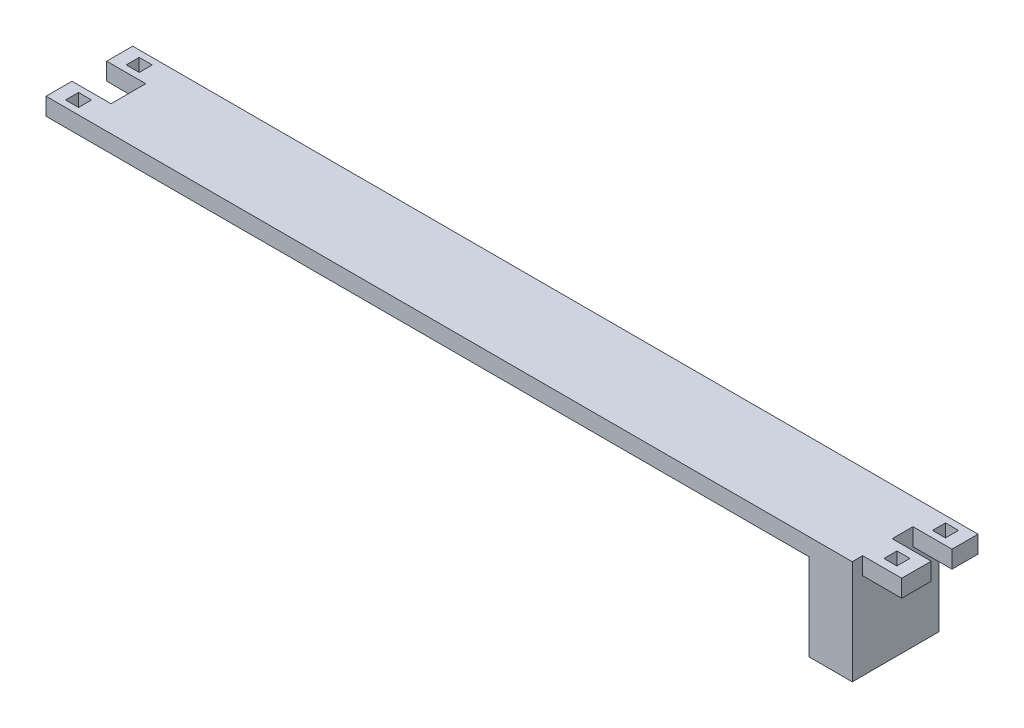
SolidWorks part; units mm, degrees
ref_plane "Front Plane" through (0, 0, 0) normal (0, 0, 1) x (1, 0, 0)
ref_plane "Top Plane" through (0, 0, 0) normal (0, 1, 0) x (1, 0, 0)
ref_plane "Right Plane" through (0, 0, 0) normal (1, 0, 0) x (0, 0, -1)
sketch "Sketch2" plane through (0, 0, 0) normal (0, 1, 0) x (1, 0, 0)
  line L1 (0, 0) -> (194.96, 0)
  line L2 (0, 0) -> (0, 6)
  line L3 (0, 6) -> (194.96, 6)
  line L4 (194.96, 0) -> (194.96, 6)
  dimension "D1" = 194.96
  dimension "D2" = 6
extrude "Boss-Extrude1" add sketch "Sketch2" along normal blind 4
sketch "Sketch3" plane through (0, 0, 0) normal (0, 0, -1) x (-1, 0, 0)
  line L0 (-194.96, 4) -> (0, 4) construction
  line L1 (-9, 4) -> (-185.96, 4)
  line L2 (-9, 4) -> (-9, 0)
  line L3 (-9, 0) -> (-185.96, 0)
  line L4 (-185.96, 4) -> (-185.96, 0)
  line L5 (-194.96, 0) -> (0, 0) construction
  line L7 (-194.96, 4) -> (-194.96, 0) construction
  line L8 (0, 4) -> (0, 0) construction
  dimension "D1" = 9
  dimension "D2" = 9
extrude "Boss-Extrude2" add sketch "Sketch3" against normal blind 14
sketch "Sketch4" plane through (9, 0, 0) normal (-1, 0, 0) x (0, 0, 1)
  line L0 (14, 0) -> (0, 0) construction
  line L1 (14, 4) -> (8, 4)
  line L2 (14, 4) -> (14, 0)
  line L3 (14, 0) -> (8, 0)
  line L4 (8, 4) -> (8, 0)
  line L6 (0, 0) -> (0, 4) construction
  dimension "D1" = 6
extrude "Boss-Extrude3" add sketch "Sketch4" along normal blind 9
sketch "Sketch5" plane through (185.96, 0, 0) normal (1, 0, 0) x (0, 0, -1)
  line L0 (-14, 4) -> (0, 4) construction
  line L1 (-11.6, 4) -> (-4.8, 4)
  line L2 (-11.6, 4) -> (-11.6, 0)
  line L3 (-11.6, 0) -> (-4.8, 0)
  line L4 (-4.8, 4) -> (-4.8, 0)
  line L5 (-14, 0) -> (0, 0) construction
  line L6 (-14, 4) -> (-14, 0) construction
  line L7 (0, 4) -> (0, 0) construction
  dimension "D1" = 2.4
  dimension "D2" = 4.8
extrude "Boss-Extrude4" add sketch "Sketch5" along normal blind 9
sketch "Sketch6" plane through (0, 4, 0) normal (0, 1, 0) x (1, 0, 0)
  line L0 (0, 6) -> (0, 0) construction
  line L1 (3, 4.5) -> (6, 4.5)
  line L2 (3, 4.5) -> (3, 1.5)
  line L3 (3, 1.5) -> (6, 1.5)
  line L4 (6, 4.5) -> (6, 1.5)
  line L5 (194.96, 6) -> (0, 6) construction
  line L7 (0, -14) -> (185.96, -14) construction
  line L8 (3, -9.5) -> (6, -9.5)
  line L9 (3, -9.5) -> (3, -12.5)
  line L10 (3, -12.5) -> (6, -12.5)
  line L11 (6, -9.5) -> (6, -12.5)
  line L12 (0, -14) -> (0, -8) construction
  line L13 (194.96, 0) -> (194.96, 6) construction
  line L14 (188.96, 4.5) -> (191.96, 4.5)
  line L15 (188.96, 4.5) -> (188.96, 1.5)
  line L16 (188.96, 1.5) -> (191.96, 1.5)
  line L17 (191.96, 4.5) -> (191.96, 1.5)
  line L18 (194.96, -4.8) -> (194.96, -11.6) construction
  line L19 (191.96, -6.7) -> (188.96, -6.7)
  line L20 (191.96, -6.7) -> (191.96, -9.7)
  line L21 (191.96, -9.7) -> (188.96, -9.7)
  line L22 (188.96, -6.7) -> (188.96, -9.7)
  line L23 (194.96, -4.8) -> (185.96, -4.8) construction
  dimension "D1" = 3
  dimension "D2" = 3
  dimension "D3" = 3
  dimension "D4" = 1.5
  dimension "D5" = 3
  dimension "D6" = 1.5
  dimension "D7" = 3
  dimension "D8" = 1.5
  dimension "D9" = 3
  dimension "D10" = 3
  dimension "D11" = 3
  dimension "D12" = 3
  dimension "D13" = 3
  dimension "D14" = 3
  dimension "D15" = 1.9
extrude "Cut-Extrude1" cut sketch "Sketch6" against normal up to next
sketch "Sketch7" plane through (0, 0, 0) normal (0, -1, 0) x (1, 0, 0)
  line L0 (194.96, -6) -> (0, -6) construction
  line L1 (185.96, 14) -> (175.96, 14)
  line L2 (185.96, 14) -> (185.96, -6)
  line L3 (185.96, -6) -> (175.96, -6)
  line L4 (175.96, 14) -> (175.96, -6)
  dimension "D1" = 10
extrude "Boss-Extrude5" add sketch "Sketch7" along normal blind 20
sketch "Sketch8" plane through (0, 0, 0) normal (0, -1, 0) x (1, 0, 0)
  line L0 (175.96, -6) -> (0, -6) construction
  line L1 (49, -6) -> (185.96, -6)
  line L2 (49, -6) -> (49, 0)
  line L3 (49, 0) -> (185.96, 0)
  line L4 (185.96, -6) -> (185.96, 0)
  line L5 (185.96, -6) -> (185.96, 14) construction
  line L6 (9, 8) -> (9, 0) construction
  dimension "D1" = 40
  dimension "D2" = 6
extrude "Boss-Extrude6" add sketch "Sketch8" along normal blind 8
chamfer "Chamfer1" distance 12 angle 50 1 edges at (175.96, -8, -3) first distance on face at (175.96, -9.3333, 2.6667)
